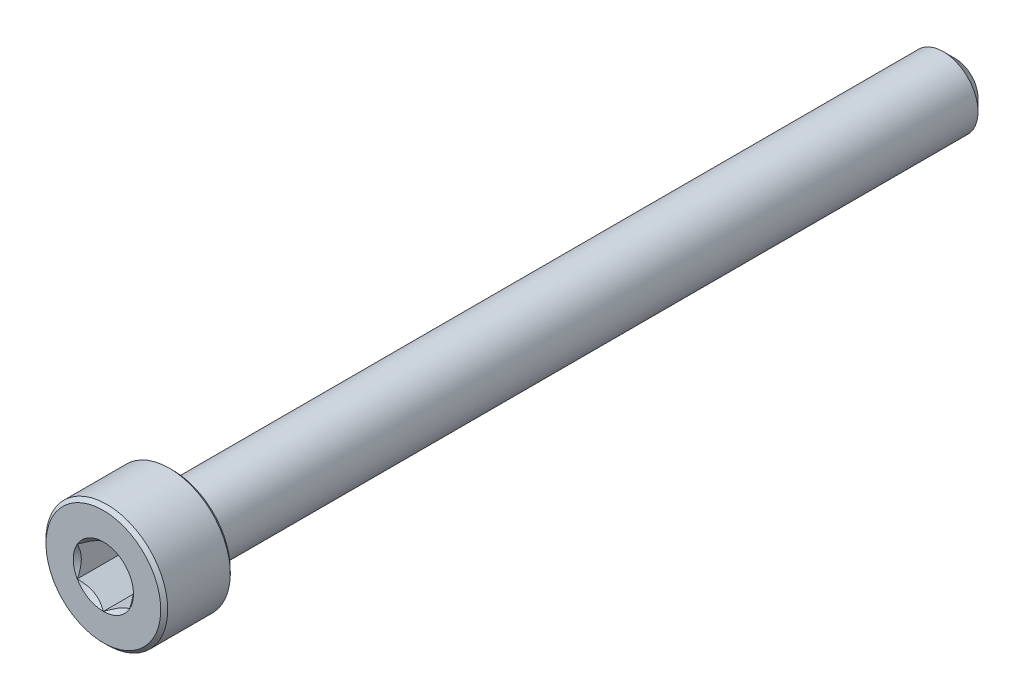
SolidWorks part; units mm, degrees
ref_plane "Front Plane" through (0, 0, 0) normal (0, 0, 1) x (1, 0, 0)
ref_plane "Top Plane" through (0, 0, 0) normal (0, 1, 0) x (1, 0, 0)
ref_plane "Right Plane" through (0, 0, 0) normal (1, 0, 0) x (0, 0, -1)
sketch "Sketch1" plane through (0, 0, 0) normal (1, 0, 0) x (0, 0, -1)
  line L0 (-24.5, 0) -> (24.5, 0) construction
  line L1 (24.5, 0) -> (24.5, 1.3) construction
  line L2 (24.5, 1.3) -> (23.8, 2) construction
  line L3 (23.8, 2) -> (23.975, 2) construction
  line L4 (23.975, 2) -> (-20.5, 2) construction
  line L5 (-20.5, 2) -> (-20.5, 3.5) construction
  line L6 (-20.5, 3.5) -> (-24.5, 3.5) construction
  line L7 (-24.5, 3.5) -> (-24.5, 0) construction
  line L8 (24.5, 1.3) -> (24.5, 2) construction
  line L9 (24.4563, 2.0758) -> (24.8063, 1.4696) construction
  line L10 (24.8063, 1.4696) -> (25.1563, 2.0758) construction
  line L11 (25.1563, 2.0758) -> (24.4563, 2.0758) construction
  line L12 (24.8063, 2.0758) -> (24.8063, 2) construction
  line L13 (24.8063, 1.4696) -> (24.8063, 1.5453) construction
  line L14 (24.7625, 1.5453) -> (24.85, 1.5453) construction
  line L15 (24.5, 2) -> (25.1125, 2) construction
  line L16 (24.4781, 2.0379) -> (25.1344, 2.0379) construction
  line L17 (24.5, 0) -> (24.5, -2) construction
  line L18 (-20.7, 3.5) -> (-20.5, 3.3) construction
  line L19 (-24.3, 3.5) -> (-24.5, 3.3) construction
  line L20 (-20.5, 2) -> (-20.5, 0) construction
  line L21 (-20.5, 1) -> (-5.5, 1) construction
  line L22 (-5.5, 1) -> (9.5, 1) construction
  line L23 (9.5, 1) -> (24.5, 1) construction
  line L24 (-5.5, 1) -> (-5.5, 2) construction
  line L25 (-5.5, 2) -> (-5.5, 3.5) construction
  line L26 (9.5, 1) -> (9.5, 3.5) construction
  point P0 (-24.5, 1.5)
  point P3 (22.75, 2)
  point P4 (0, 0)
  point P18 (9.5, 2)
  point P22 (24.8063, 1.5453)
  point P24 (23.975, 2)
  point P25 (24.8063, 2)
  point P28 (24.8063, 2.0379)
  point P29 (22.75, -2)
  point P30 (-5.5, 2)
  point P31 (-22.5, 3.5)
  point P37 (-21.2, 3.5)
  point P38 (-24.2, 3.5)
  point P45 (-5.5, 1)
  point P46 (9.5, 1)
  dimension "D1" = 45
  dimension "D2" = 0.0875
  dimension "D3" = 0.7
  dimension "D7" = 0.2
  dimension "D8" = 0.2
  dimension "D9" = 0.2
  dimension "D10" = 0.1
  dimension "D11" = 0.5
  dimension "Drive Size" = 3
  dimension "Head Diameter" = 7
  dimension "Head Height" = 4
  dimension "Thread Pitch" = 0.7
  dimension "Thread Major Diameter" = 4
  dimension "Length" = 45
  dimension "D12" = 0.525
  dimension "D4" = 1.75
sketch "Sketch2" plane through (0, 0, 0) normal (1, 0, 0) x (0, 0, -1)
  line L0 (-24.5, 0) -> (-24.5, 3.3)
  line L1 (-24.3, 3.5) -> (-20.7, 3.5)
  line L2 (-20.5, 3.3) -> (-20.5, 2)
  line L3 (-20.5, 2) -> (23.8, 2)
  line L4 (23.8, 2) -> (24.5, 1.3)
  line L5 (24.5, 1.3) -> (24.5, 0)
  line L6 (-20.7, 3.5) -> (-20.5, 3.3) construction
  line L7 (24.5, 0) -> (-24.5, 0)
  line L8 (-24.3, 3.5) -> (-24.5, 3.3) construction
  line L9 (-20.7, 3.5) -> (-20.5, 3.3)
  line L10 (-24.3, 3.5) -> (-24.5, 3.3)
revolve "Revolve1" add sketch "Sketch2" angle 360 about L7
sketch "Sketch3" plane through (0, 0, 24.5) normal (0, 0, 1) x (1, 0, 0)
  line L1 (1.5, -0.866) -> (1.5, 0.866)
  line L2 (1.5, 0.866) -> (0, 1.7321)
  line L3 (0, 1.7321) -> (-1.5, 0.866)
  line L4 (-1.5, 0.866) -> (-1.5, -0.866)
  line L5 (-1.5, -0.866) -> (0, -1.7321)
  line L6 (0, -1.7321) -> (1.5, -0.866)
  circle A0 centre (0, 0) radius 1.5 construction
extrude "Cut-Extrude1" cut sketch "Sketch3" against normal offset from surface (3 mm away) 1 up to face at (0, 3.3, 20.5)
sketch "Sketch4" plane through (0, 0, 24.5) normal (0, 0, 1) x (1, 0, 0)
  circle A0 centre (0, 0) radius 1.7321
extrude "Cut-Extrude2" cut sketch "Sketch4" against normal up to vertex (2 mm away) draft 45 up to point (0, 3.5, 22.5)
ref_plane "Plane1" [suppressed] through (0, 0, -23.975) normal (0, 0, 1) x (1, 0, 0)
split "Split1" [suppressed] bodies to split 106
sketch "Sketch6" [suppressed] plane through (0, 0, -24.5) normal (0, 0, -1) x (-1, 0, 0)
  circle A0 centre (0, 0) radius 2
curve "Helix/Spiral1" [suppressed] pitch 0.7 height 45.805 turns 65.4357
sketch "Sketch7" [suppressed] plane through (0, 0, 0) normal (1, 0, 0) x (0, 0, -1)
  line L0 (24.4781, 2.0379) -> (25.1344, 2.0379)
  line L1 (25.1344, 2.0379) -> (24.85, 1.5453)
  line L2 (24.85, 1.5453) -> (24.7625, 1.5453)
  line L3 (24.7625, 1.5453) -> (24.4781, 2.0379)
sweep "Cut-Sweep1" [suppressed] cut profiles "Sketch7" path "Helix/Spiral1"
sketch "Sketch8" [suppressed] plane through (0, 0, 20.5) normal (0, 0, -1) x (-1, 0, 0)
  circle A0 centre (0, 0) radius 2
extrude "Boss-Extrude1" [suppressed] add sketch "Sketch8" along normal through all draft 45
equation "\"D2@Sketch1\" = \"Thread Pitch@Sketch1\" / 8"
equation "\"D3@Sketch1\"= \"Thread Pitch@Sketch1\""
equation "\"D4@Helix/Spiral1\" = \"Thread Pitch@Sketch1\""
equation "\"D7@Sketch1\" = \"Head Height@Sketch1\" * .05"
equation "\"D8@Sketch1\"=\"D7@Sketch1\""
equation "\"D9@Sketch1\"=\"D7@Sketch1\""
equation "\"D10@Sketch1\"=\"D7@Sketch1\"/2"
equation "\"D11@Sketch1\"=\"D10@Sketch1\"*5"
equation "\"D4@Sketch1\"=\"Thread Pitch@Sketch1\"*2.5"
equation "\"D12@Sketch1\"=\"Thread Pitch@Sketch1\"*.75"
